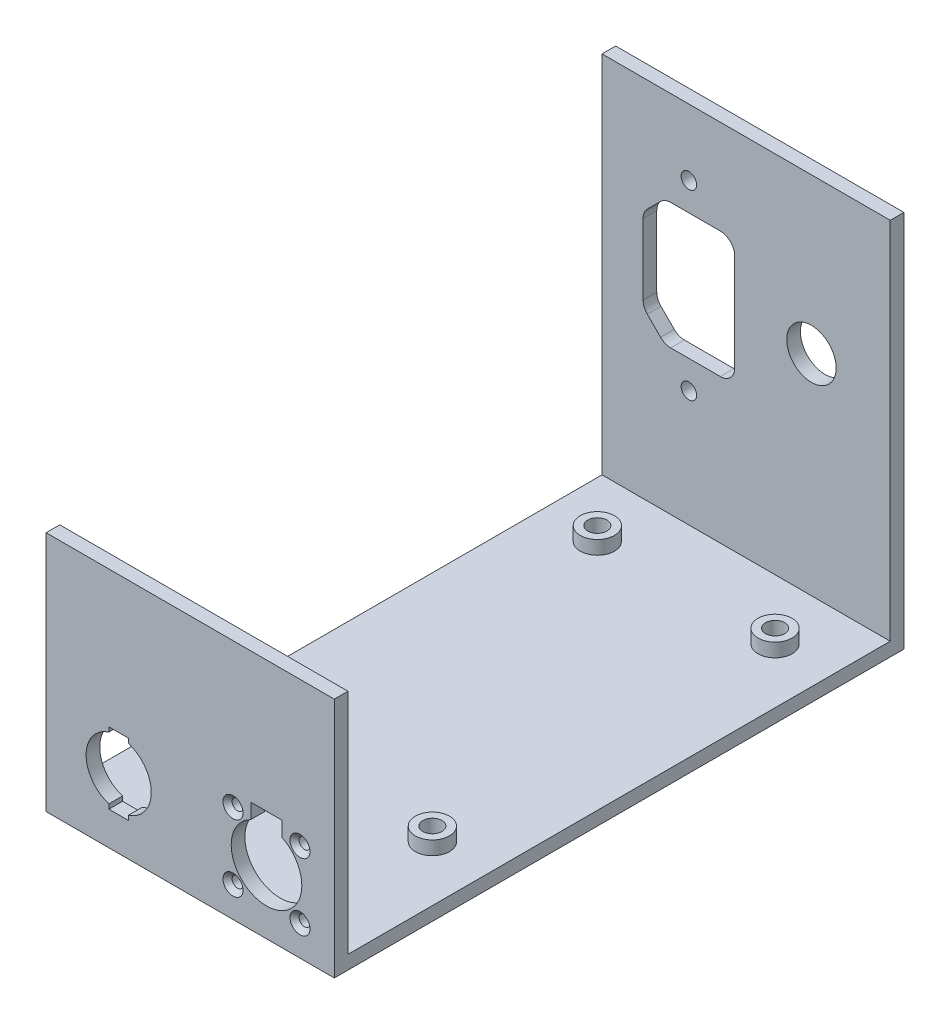
SolidWorks part; units mm, degrees
ref_plane "Спереди" through (0, 0, 0) normal (0, 0, 1) x (1, 0, 0)
ref_plane "Сверху" through (0, 0, 0) normal (0, 1, 0) x (1, 0, 0)
ref_plane "Справа" through (0, 0, 0) normal (1, 0, 0) x (0, 0, -1)
sketch "Эскиз2" plane through (0, 0, 0) normal (0, -1, 0) x (1, 0, 0)
  circle A0 centre (19.5, 37.6) radius 3.75
  circle A1 centre (19.5, -37.6) radius 3.75
  circle A2 centre (-19.5, -37.6) radius 3.75
  circle A3 centre (-19.5, 37.6) radius 3.75
  dimension "D1" = 7.5
extrude "Бобышка-Вытянуть1" add sketch "Эскиз2" along normal blind 3
sketch "Эскиз3" plane through (0, -3, 0) normal (0, -1, 0) x (1, 0, 0)
  line L0 (26.625, 41.25) -> (26.625, -41.25) construction
  line L1 (-31.625, 71.25) -> (31.625, 71.25)
  line L2 (-31.625, 71.25) -> (-31.625, -53.75)
  line L3 (-31.625, -53.75) -> (31.625, -53.75)
  line L4 (31.625, 71.25) -> (31.625, -53.75)
  line L5 (-31.625, 71.25) -> (31.625, -53.75) construction
  line L6 (-31.625, -53.75) -> (31.625, 71.25) construction
  line L8 (-23.625, 41.25) -> (23.625, 41.25) construction
  line L9 (-26.625, 41.25) -> (-26.625, -41.25) construction
  point P0 (0, 8.75)
  dimension "D1" = 5
  dimension "D2" = 125
  dimension "D3" = 30
  dimension "D4" = 5
extrude "Бобышка-Вытянуть2" add sketch "Эскиз3" along normal blind 3
sketch "Эскиз4" plane through (0, 0, 0) normal (0, 1, 0) x (1, 0, 0)
  circle A0 centre (19.5, 37.6) radius 2.1
  circle A1 centre (19.5, -37.6) radius 2.1
  circle A2 centre (-19.5, -37.6) radius 2.1
  circle A3 centre (-19.5, 37.6) radius 2.1
  dimension "D1" = 4.2
extrude "Вырез-Вытянуть1" cut sketch "Эскиз4" against normal blind 4
sketch "Эскиз5" plane through (0, -3, 0) normal (0, 1, 0) x (1, 0, 0)
  line L0 (31.625, 53.75) -> (31.625, -71.25) construction
  line L1 (-31.625, -71.25) -> (31.625, -71.25)
  line L2 (-31.625, -71.25) -> (-31.625, -68.25)
  line L3 (-31.625, -68.25) -> (31.625, -68.25)
  line L4 (31.625, -71.25) -> (31.625, -68.25)
  dimension "D1" = 3
extrude "Бобышка-Вытянуть3" add sketch "Эскиз5" along normal blind 50
sketch "Эскиз8" plane through (0, 0, 71.25) normal (0, 0, 1) x (1, 0, 0)
  line L6 (20.1954, 14.9397) -> (20.1954, 18.25)
  line L7 (20.1954, 18.25) -> (13.2954, 18.25)
  line L8 (13.2954, 18.25) -> (13.2954, 14.9397)
  line L9 (20.1954, 14.9397) -> (20.1954, 18.25)
  line L10 (20.1954, 18.25) -> (13.2954, 18.25)
  line L11 (13.2954, 18.25) -> (13.2954, 14.9397)
  arc A2 (13.2954, 14.9397) -> (20.1954, 14.9397) centre (16.7454, 8) ccw
  arc A3 (13.2954, 14.9397) -> (20.1954, 14.9397) centre (16.7454, 8) ccw
  dimension "D1" = 0.15
extrude "Вырез-Вытянуть2" cut sketch "Эскиз8" against normal blind 10
hole_wizard "Зенковка для винта с полупотайной головкой M21" positions "Эскиз9" profile "Эскиз11" countersink size "M2" standard "DIN"
sketch "Эскиз9" plane through (0, 0, 71.25) normal (0, 0, 1) x (1, 0, 0)
  circle A0 centre (9.3954, 0.65) radius 1.2 construction
  circle A1 centre (24.0954, 0.65) radius 1.2 construction
  circle A2 centre (9.3954, 15.35) radius 1.2 construction
  circle A3 centre (24.0954, 15.35) radius 1.2 construction
  circle A4 centre (9.3954, 0.65) radius 1.2 construction
  circle A5 centre (24.0954, 0.65) radius 1.2 construction
  circle A6 centre (9.3954, 15.35) radius 1.2 construction
  circle A7 centre (24.0954, 15.35) radius 1.2 construction
  point P1 (9.3954, 0.65)
  point P3 (24.0954, 0.65)
  point P5 (9.3954, 15.35)
  point P7 (24.0954, 15.35)
sketch "Эскиз11" plane through (9.3954, 0.65, 71.25) normal (1, 0, 0) x (0, -1, 0)
  line L0 (0, 0) -> (0, 5.721)
  line L1 (0, 5.721) -> (1.2, 5)
  line L2 (1.2, 5) -> (1.2, 1)
  line L3 (1.2, 1) -> (2.2, 0)
  line L5 (2.2, 0) -> (0, 0)
  line L6 (-1.2, 1) -> (-2.2, 0) construction
  line L10 (0, 5.721) -> (-1.2, 5) construction
  line L11 (0, -6.35) -> (0, 107.95) construction
  dimension "Диаметр отверстия" = 2.4
  dimension "Глубина отверстия" = 5
  dimension "Диаметр передней зенковки" = 4.4
  dimension "Угол передней зенковки" = 90
  dimension "Угол заточки сверла" = 118
sketch "Эскиз12" plane through (0, -3, 0) normal (0, 1, 0) x (1, 0, 0)
  line L0 (-31.625, -68.25) -> (-31.625, 53.75) construction
  line L1 (31.625, 53.75) -> (-31.625, 53.75)
  line L2 (31.625, 53.75) -> (31.625, 50.75)
  line L3 (31.625, 50.75) -> (-31.625, 50.75)
  line L4 (-31.625, 53.75) -> (-31.625, 50.75)
  dimension "D1" = 3
extrude "Бобышка-Вытянуть4" add sketch "Эскиз12" along normal blind 80
sketch "Эскиз13" plane through (0, 0, -50.75) normal (0, 0, 1) x (1, 0, 0)
  line L12 (-16.5476, 28.6612) -> (-5.6652, 28.6612)
  line L13 (-2.5152, 31.8112) -> (-2.5152, 53.1612)
  line L14 (-5.6652, 56.3112) -> (-16.5476, 56.3112)
  line L15 (-18.775, 55.3886) -> (-21.6926, 52.471)
  line L16 (-22.6152, 50.2436) -> (-22.6152, 34.7289)
  line L17 (-21.6926, 32.5015) -> (-18.775, 29.5839)
  line L18 (-16.5476, 28.6612) -> (-5.6652, 28.6612)
  line L19 (-2.5152, 31.8112) -> (-2.5152, 53.1612)
  line L20 (-5.6652, 56.3112) -> (-16.5476, 56.3112)
  line L21 (-18.775, 55.3886) -> (-21.6926, 52.471)
  line L22 (-22.6152, 50.2436) -> (-22.6152, 34.7289)
  line L23 (-21.6926, 32.5015) -> (-18.775, 29.5839)
  arc A12 (-18.775, 29.5839) -> (-16.5476, 28.6612) centre (-16.5476, 31.8112) ccw
  arc A13 (-5.6652, 28.6612) -> (-2.5152, 31.8112) centre (-5.6652, 31.8112) ccw
  arc A14 (-2.5152, 53.1612) -> (-5.6652, 56.3112) centre (-5.6652, 53.1612) ccw
  arc A15 (-16.5476, 56.3112) -> (-18.775, 55.3886) centre (-16.5476, 53.1612) ccw
  arc A16 (-21.6926, 52.471) -> (-22.6152, 50.2436) centre (-19.4652, 50.2436) ccw
  arc A17 (-22.6152, 34.7289) -> (-21.6926, 32.5015) centre (-19.4652, 34.7289) ccw
  arc A18 (-18.775, 29.5839) -> (-16.5476, 28.6612) centre (-16.5476, 31.8112) ccw
  arc A19 (-5.6652, 28.6612) -> (-2.5152, 31.8112) centre (-5.6652, 31.8112) ccw
  arc A20 (-2.5152, 53.1612) -> (-5.6652, 56.3112) centre (-5.6652, 53.1612) ccw
  arc A21 (-16.5476, 56.3112) -> (-18.775, 55.3886) centre (-16.5476, 53.1612) ccw
  arc A22 (-21.6926, 52.471) -> (-22.6152, 50.2436) centre (-19.4652, 50.2436) ccw
  arc A23 (-22.6152, 34.7289) -> (-21.6926, 32.5015) centre (-19.4652, 34.7289) ccw
  dimension "D1" = 0.15
extrude "Вырез-Вытянуть3" cut sketch "Эскиз13" against normal through all
hole_wizard "Отверстие с зазором M31" positions "Эскиз14" profile "Эскиз15" hole size "M3" standard "DIN"
sketch "Эскиз14" plane through (0, 0, -53.75) normal (0, 0, -1) x (-1, 0, 0)
  point P0 (12.5652, 22.4862)
  point P3 (12.5652, 62.4862)
sketch "Эскиз15" plane through (-12.5652, 22.4862, -53.75) normal (1, 0, 0) x (0, 1, 0)
  line L0 (0, 0) -> (0, 11.0215)
  line L1 (0, 11.0215) -> (1.7, 10)
  line L2 (1.7, 10) -> (1.7, 0)
  line L5 (1.7, 0) -> (0, 0)
  line L10 (0, 11.0215) -> (-1.7, 10) construction
  line L11 (0, -6.35) -> (0, 107.95) construction
  dimension "Диаметр отверстия" = 3.4
  dimension "Глубина отверстия" = 10
  dimension "Угол заточки сверла" = 118
sketch "Эскиз16" plane through (0, 0, -50.75) normal (0, 0, 1) x (1, 0, 0)
  circle A2 centre (14.3322, 42.9731) radius 5.425
  circle A3 centre (14.3322, 42.9731) radius 5.425
  dimension "D1" = 0.15
extrude "Вырез-Вытянуть4" cut sketch "Эскиз16" against normal through all
sketch "Эскиз17" plane through (0, 0, 68.25) normal (0, 0, -1) x (-1, 0, 0)
  line L2 (17.6969, 0.8798) -> (13.6969, 0.8798) construction
  line L3 (17.6969, 17.4672) -> (13.6969, 17.4672) construction
  line L8 (17.6969, 1.0406) -> (17.6969, 0.8798) construction
  line L9 (13.6969, 1.0406) -> (13.6969, 0.8798) construction
  line L10 (13.6969, 17.3064) -> (13.6969, 17.4672) construction
  line L11 (17.6969, 17.3064) -> (17.6969, 17.4672) construction
  line L12 (17.6969, 0.8798) -> (13.6969, 0.8798) construction
  line L13 (17.6969, 17.4672) -> (13.6969, 17.4672) construction
  line L14 (17.6969, 2.4653) -> (17.6969, 0.8798) construction
  line L15 (13.6969, 2.4653) -> (13.6969, 0.8798) construction
  line L16 (13.6969, 15.8817) -> (13.6969, 17.4672) construction
  line L17 (17.6969, 15.8817) -> (17.6969, 17.4672) construction
  line L18 (13.5469, 15.9926) -> (13.5469, 16.9926)
  line L19 (13.5469, 2.3544) -> (13.5469, 1.3544)
  line L22 (17.8469, 2.3544) -> (17.8469, 1.3544)
  line L23 (17.8469, 15.9926) -> (17.8469, 16.9926)
  line L24 (17.8469, 15.9926) -> (17.8469, 17.4672) construction
  line L25 (13.5469, 15.9926) -> (13.5469, 17.4672) construction
  line L26 (17.8469, 16.9926) -> (13.5469, 16.9926)
  line L27 (13.5469, 2.3544) -> (13.5469, 0.8798) construction
  line L28 (17.8469, 2.3544) -> (17.8469, 0.8798) construction
  line L29 (17.8469, 1.3544) -> (13.5469, 1.3544)
  arc A0 (18.8493, 2.9235) -> (18.8493, 15.4235) centre (15.6969, 9.1735) ccw construction
  arc A1 (13.6969, 15.8817) -> (13.6969, 2.4653) centre (15.6969, 9.1735) ccw construction
  arc A2 (17.6969, 2.4653) -> (17.6969, 15.8817) centre (15.6969, 9.1735) ccw construction
  arc A5 (13.5469, 15.9926) -> (13.5469, 2.3544) centre (15.6969, 9.1735) ccw
  arc A6 (17.8469, 2.3544) -> (17.8469, 15.9926) centre (15.6969, 9.1735) ccw
  dimension "D2" = 1
  dimension "D3" = 1
  dimension "D1" = 0.15
extrude "Вырез-Вытянуть5" cut sketch "Эскиз17" against normal through all
